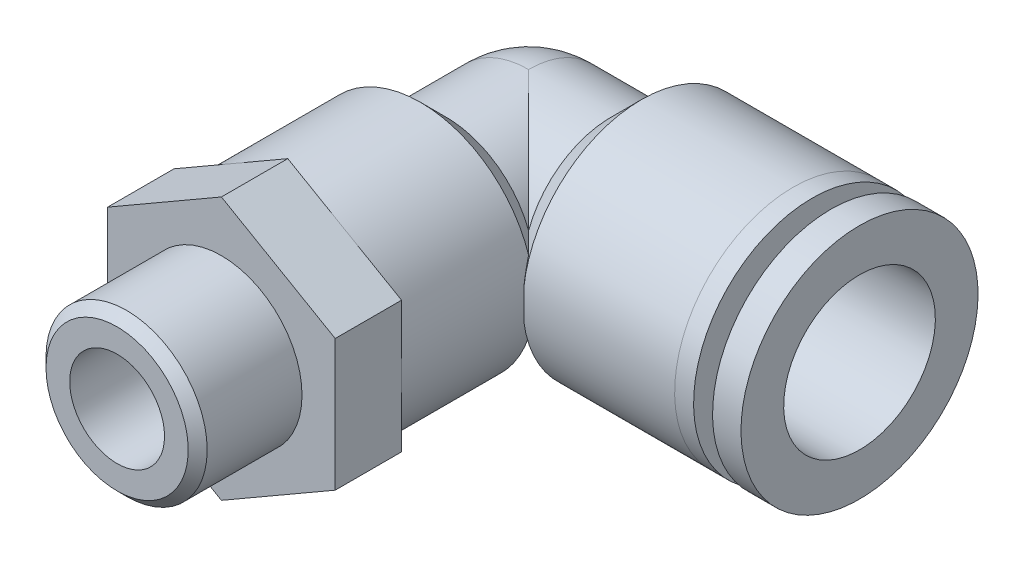
SolidWorks part; units mm, degrees
ref_plane "Front Plane" through (0, 0, 0) normal (0, 0, 1) x (1, 0, 0)
ref_plane "Top Plane" through (0, 0, 0) normal (0, 1, 0) x (1, 0, 0)
ref_plane "Right Plane" through (0, 0, 0) normal (1, 0, 0) x (0, 0, -1)
sketch "Sketch1" plane through (0, 0, 0) normal (0, 0, 1) x (1, 0, 0)
  line L1 (0, 7.3819) -> (6.9056, 7.3819)
  line L2 (6.9056, 7.3819) -> (9.4456, 9.9219)
  line L3 (9.4456, 9.9219) -> (22.1456, 9.9219)
  line L4 (22.1456, 9.9219) -> (22.1456, 7.1438)
  line L5 (22.1456, 7.1438) -> (25.3206, 7.1438)
  line L6 (25.3206, 7.1438) -> (25.3206, 9.9219)
  line L7 (25.3206, 9.9219) -> (27.7019, 9.9219)
  line L8 (27.7019, 9.9219) -> (27.7019, 0)
  line L9 (27.7019, 0) -> (-7.3819, 0)
  arc A0 (0, 7.3819) -> (-7.3819, 0) centre (0, 0) ccw
  dimension "D9" = 7.3819
  dimension "D2" = 2.54
  dimension "D3" = 2.54
  dimension "D4" = 9.9219
  dimension "D5" = 2.3813
  dimension "D6" = 18.2562
  dimension "D7" = 3.175
  dimension "D8" = 7.1437
revolve "Revolve1" add sketch "Sketch1" angle 360 about L9
sketch "Sketch4" plane through (0, 0, 0) normal (1, 0, 0) x (0, 0, -1)
  line L0 (7.3819, 0) -> (-20.1612, 0)
  line L1 (-20.1612, 0) -> (-20.1612, 9.525)
  line L2 (-20.1612, 9.525) -> (-9.0487, 9.525)
  line L3 (-9.0487, 9.525) -> (-6.9056, 7.3819)
  line L4 (-6.9056, 7.3819) -> (0, 7.3819)
  circle A0 centre (0, 0) radius 7.3819 construction
  arc A1 (7.3819, 0) -> (0, 7.3819) centre (0, 0) ccw
  dimension "D1" = 14.2875
  dimension "D2" = 9.525
  dimension "D4" = 45
  dimension "D6" = 11.1125
revolve "Revolve3" add sketch "Sketch4" angle 360 about L0
sketch "Sketch2" plane through (22.1456, 0, 0) normal (1, 0, 0) x (0, 0, -1)
  circle A0 centre (0, 0) radius 7.1438
  circle A1 centre (0, 0) radius 9.9219
  dimension "D1" = 14.2875
  dimension "D2" = 19.8438
extrude "Extrude1" add sketch "Sketch2" along normal blind 1.5875 separate body
sketch "Sketch7" plane through (27.7019, 0, 0) normal (1, 0, 0) x (0, 0, -1)
  circle A0 centre (0, 0) radius 6.35
  dimension "D1" = 12.7
extrude "Cut-Extrude1" cut sketch "Sketch7" against normal blind 22.225
sketch "Sketch5" plane through (0, 0, 20.1612) normal (0, 0, 1) x (1, 0, 0)
  line L1 (0, 10.9985) -> (-9.525, 5.4993)
  line L2 (-9.525, 5.4993) -> (-9.525, -5.4993)
  line L3 (-9.525, -5.4993) -> (0, -10.9985)
  line L4 (0, -10.9985) -> (9.525, -5.4993)
  line L5 (9.525, -5.4993) -> (9.525, 5.4993)
  line L6 (9.525, 5.4993) -> (0, 10.9985)
  circle A0 centre (0, 0) radius 9.525 construction
extrude "Extrude2" add sketch "Sketch5" along normal blind 5.5562 separate body
sketch "Sketch6" plane through (0, 0, 25.7175) normal (0, 0, 1) x (1, 0, 0)
  circle A0 centre (0, 0) radius 6.7469
  dimension "D1" = 13.4937
extrude "Extrude3" add sketch "Sketch6" along normal blind 8.7312
chamfer "Chamfer1" distance 0.7937 angle 45 1 edges at (6.7469, 0, 34.4487)
sketch "Sketch9" plane through (0, 0, 34.4487) normal (0, 0, 1) x (1, 0, 0)
  circle A0 centre (0, 0) radius 3.9688
  dimension "D1" = 7.9375
extrude "Cut-Extrude2" cut sketch "Sketch9" against normal up to next (14.2875 mm away)
other "CPoint1" parameters "Diameter"=12.7, "StubLength"=0
ref_axis "Axis1" through (37.7019, 0, 0) along (-1, 0, 0)
